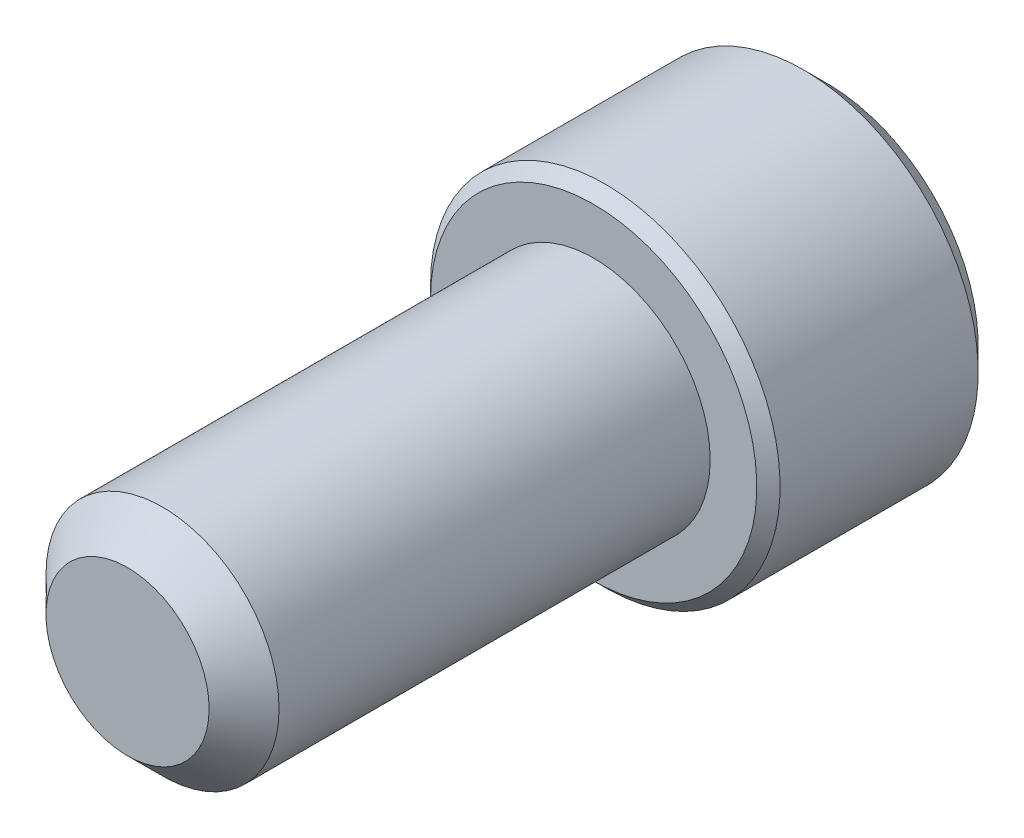
SolidWorks part; units mm, degrees
ref_plane "Front Plane" through (0, 0, 0) normal (0, 0, 1) x (1, 0, 0)
ref_plane "Top Plane" through (0, 0, 0) normal (0, 1, 0) x (1, 0, 0)
ref_plane "Right Plane" through (0, 0, 0) normal (1, 0, 0) x (0, 0, -1)
sketch "Sketch1" plane through (0, 0, 0) normal (0, 0, 1) x (1, 0, 0)
  line L0 (0, 3.175) -> (0, -3.175) construction
  circle A0 centre (0, 0) radius 3.175
  dimension "OD" = 6.35
extrude "Extrude1" add sketch "Sketch1" against normal blind 12.7
sketch "Sketch2" plane through (0, 0, 0) normal (0, 0, 1) x (1, 0, 0)
  circle A0 centre (0, 0) radius 3.175 construction
  circle A1 centre (0, 0) radius 3.175
curve "Helix/Spiral1" pitch 1.27 height 13.97 turns 11 parameters "pitch"=1.27
chamfer "Chamfer3" distance 0.9525 angle 45 1 edges at (3.175, 0, 0)
sketch "Sketch3" plane through (0, 0, 0) normal (1, 0, 0) x (0, 0, -1)
  line L0 (-1.1113, 3.175) -> (-0.635, 2.3501)
  line L1 (-0.635, 2.3501) -> (-0.4763, 2.3501)
  line L2 (-0.4763, 2.3501) -> (0, 3.175)
  line L3 (-1.1113, 3.175) -> (0, 3.175)
  line L4 (-0.5556, 3.175) -> (-0.5556, 2.3501) construction
  line L5 (-0.8731, 2.7626) -> (-0.2381, 2.7626) construction
  line L6 (0, 3.175) -> (0, -3.175) construction
  dimension "D2" = 0.635
  dimension "D3" = 60
sweep "Cut-Sweep1" [suppressed] cut profiles "Sketch3" path "Helix/Spiral1"
sketch "Sketch6" plane through (0, 0, -12.7) normal (0, 0, -1) x (-1, 0, 0)
  circle A0 centre (0, 0) radius 4.7625
  dimension "head dia" = 9.525
extrude "Extrude2" add sketch "Sketch6" along normal blind 6.35
sketch "Sketch7" plane through (0, 0, -19.05) normal (0, 0, -1) x (-1, 0, 0)
  line L1 (0, 2.7496) -> (-2.3813, 1.3748)
  line L2 (-2.3813, 1.3748) -> (-2.3813, -1.3748)
  line L3 (-2.3813, -1.3748) -> (0, -2.7496)
  line L4 (0, -2.7496) -> (2.3813, -1.3748)
  line L5 (2.3813, -1.3748) -> (2.3813, 1.3748)
  line L6 (2.3813, 1.3748) -> (0, 2.7496)
  circle A0 centre (0, 0) radius 2.3813 construction
  dimension "hex dia" = 4.7625
extrude "Cut-Extrude1" cut sketch "Sketch7" against normal blind 3.5719
sketch "Sketch8" plane through (0, 0, -19.05) normal (0, 0, -1) x (-1, 0, 0)
  circle A0 centre (0, 0) radius 2.7496
extrude "Cut-Extrude2" cut sketch "Sketch8" against normal blind 0.635 draft 45
chamfer "Chamfer1" distance 0.635 angle 45 1 edges at (-4.7625, 0, -19.05)
chamfer "Chamfer2" distance 0.3175 angle 45 1 edges at (-4.7625, 0, -12.7)
sketch "Sketch9" plane through (0, 0, 0) normal (1, 0, 0) x (0, 0, -1)
  line L0 (0, 3.175) -> (0, -3.175) construction
  line L1 (6.985, 3.175) -> (6.985, -3.175) construction
  line L2 (12.7, 4.7625) -> (12.7, -4.7625) construction
  line L3 (19.05, 4.7625) -> (19.05, -4.7625) construction
  line L4 (19.05, 0) -> (0, 0) construction
  dimension "D1" = 6.985
  dimension "D2" = 6.35
  dimension "D3" = 9.525
  dimension "D4" = 12.7
equation "\"D3@Helix/Spiral1\" = \"screw length@Extrude1\"+\"pitch@Helix/Spiral1\""
equation "\"D1@Sketch3\" = \"pitch@Helix/Spiral1\"*.125"
equation "\"D2@Sketch3\" = \"pitch@Helix/Spiral1\"*.5"
equation "\"D1@Cut-Extrude1\" = \"hex dia@Sketch7\"*.75"
equation "\"D1@Chamfer1\" = \"head depth@Extrude2\"/10"
equation "\"D1@Sketch9\" = \"pitch@Helix/Spiral1\"*5.5"
equation "\"D1@Chamfer2\" = \"D1@Chamfer1\"/2"
equation "\"D1@Cut-Extrude2\" = \"D1@Chamfer2\"*2"
equation "\"D1@Chamfer3\" = \"pitch@Helix/Spiral1\"*.750"
equation "\"D2@Sketch9\" = \"head depth@Extrude2\""
equation "\"D3@Sketch9\" = \"head dia@Sketch6\""
equation "\"D4@Sketch9\" = \"screw length@Extrude1\""
